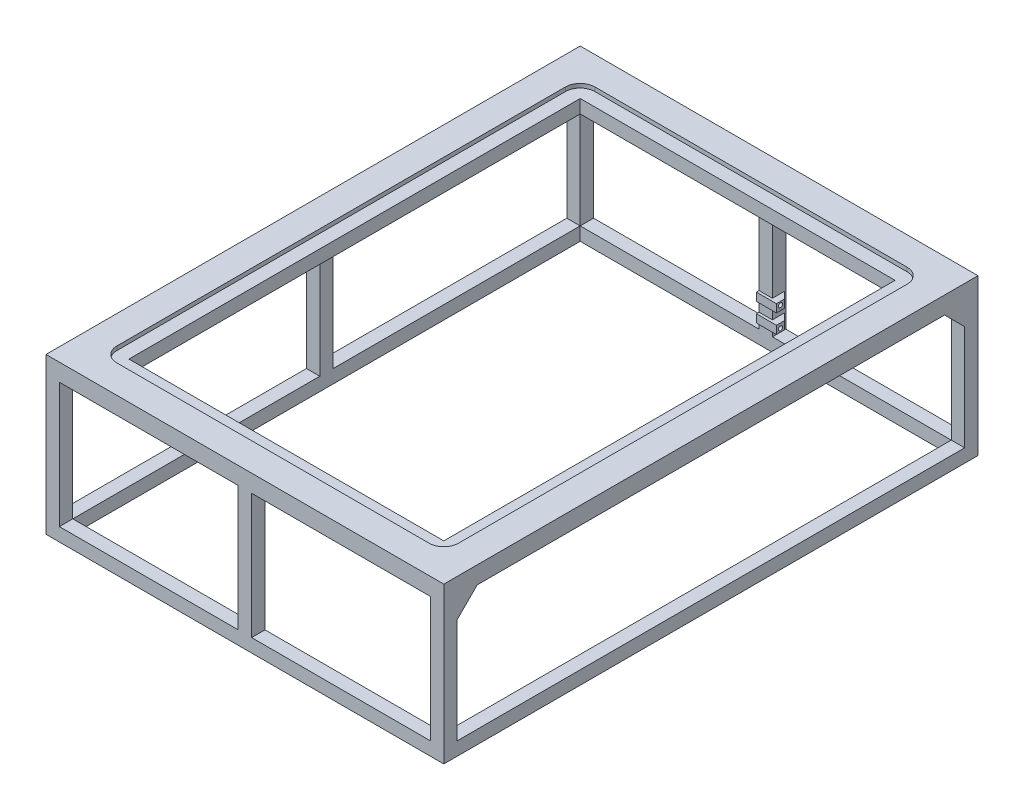
SolidWorks part; units mm, degrees
ref_plane "Front Plane" through (0, 0, 0) normal (0, 0, 1) x (1, 0, 0)
ref_plane "Top Plane" through (0, 0, 0) normal (0, 1, 0) x (1, 0, 0)
ref_plane "Right Plane" through (0, 0, 0) normal (1, 0, 0) x (0, 0, -1)
sketch "Sketch1" plane through (0, 0, 0) normal (0, 1, 0) x (1, 0, 0)
  line L1 (0, 0) -> (253.5, 0)
  line L2 (0, 0) -> (0, 355.5)
  line L3 (0, 355.5) -> (253.5, 355.5)
  line L4 (253.5, 0) -> (253.5, 355.5)
  line L5 (-22, 377.5) -> (275.5, 377.5)
  line L6 (-22, 377.5) -> (-22, -22)
  line L7 (-22, -22) -> (275.5, -22)
  line L8 (275.5, 377.5) -> (275.5, -22)
  line L9 (-12, 367.5) -> (265.5, 367.5)
  line L10 (-12, 367.5) -> (-12, -12)
  line L11 (-12, -12) -> (265.5, -12)
  line L12 (265.5, 367.5) -> (265.5, -12)
  dimension "D1" = 253.5
  dimension "D2" = 355.5
  dimension "D3" = 22
  dimension "D4" = 22
  dimension "D5" = 22
  dimension "D6" = 22
  dimension "D7" = 10
  dimension "D8" = 10
  dimension "D9" = 10
  dimension "D10" = 10
extrude "Boss-Extrude1" add sketch "Sketch1" along normal blind 10 contours L8 L5 L6 L7 L9 L12 L11 L10 region at (126.75, 0, -372.519)
sketch "Sketch2" plane through (0, 10, 0) normal (0, 1, 0) x (1, 0, 0)
  line L0 (-22, -22) -> (275.5, -22) construction
  line L1 (131.75, -22) -> (121.75, -22)
  line L2 (131.75, -22) -> (131.75, -12)
  line L3 (131.75, -12) -> (121.75, -12)
  line L4 (121.75, -22) -> (121.75, -12)
  line L5 (-12, -12) -> (265.5, -12) construction
  line L6 (-12, 367.5) -> (265.5, 367.5) construction
  line L7 (275.5, -22) -> (265.5, -22)
  line L8 (275.5, -22) -> (275.5, -12)
  line L9 (275.5, -12) -> (265.5, -12)
  line L10 (265.5, -22) -> (265.5, -12)
  line L11 (-22, -22) -> (-12, -22)
  line L12 (-22, -22) -> (-22, -12)
  line L13 (-22, -12) -> (-12, -12)
  line L14 (-12, -22) -> (-12, -12)
  line L15 (-22, 377.5) -> (-12, 377.5)
  line L16 (-22, 377.5) -> (-22, 367.5)
  line L17 (-22, 367.5) -> (-12, 367.5)
  line L18 (-12, 377.5) -> (-12, 367.5)
  line L19 (275.5, 377.5) -> (265.5, 377.5)
  line L20 (275.5, 377.5) -> (275.5, 367.5)
  line L21 (275.5, 367.5) -> (265.5, 367.5)
  line L22 (265.5, 377.5) -> (265.5, 367.5)
  line L23 (131.75, 367.5) -> (121.75, 367.5)
  line L24 (131.75, 367.5) -> (131.75, 377.5)
  line L25 (131.75, 377.5) -> (121.75, 377.5)
  line L26 (121.75, 367.5) -> (121.75, 377.5)
  line L27 (-22, 377.5) -> (275.5, 377.5) construction
  line L28 (275.5, 377.5) -> (275.5, -22) construction
  line L29 (275.5, 172.75) -> (265.5, 172.75)
  line L30 (275.5, 172.75) -> (275.5, 182.75)
  line L31 (275.5, 182.75) -> (265.5, 182.75)
  line L32 (265.5, 172.75) -> (265.5, 182.75)
  line L33 (265.5, 367.5) -> (265.5, -12) construction
  line L34 (-12, 367.5) -> (-12, -12) construction
  line L35 (-12, 172.75) -> (-22, 172.75)
  line L36 (-12, 172.75) -> (-12, 182.75)
  line L37 (-12, 182.75) -> (-22, 182.75)
  line L38 (-22, 172.75) -> (-22, 182.75)
  line L39 (-22, 377.5) -> (-22, -22) construction
  dimension "D1" = 133.75
  dimension "D2" = 10
  dimension "D3" = 133.75
  dimension "D4" = 10
  dimension "D5" = 133.75
  dimension "D6" = 10
  dimension "D7" = 184.75
  dimension "D8" = 184.75
  dimension "D9" = 10
  dimension "D10" = 184.75
extrude "Boss-Extrude2" add sketch "Sketch2" along normal blind 93.5
sketch "Sketch3" plane through (0, 103.5, 0) normal (0, 1, 0) x (1, 0, 0)
  line L1 (-22, 377.5) -> (275.5, 377.5)
  line L2 (-22, 377.5) -> (-22, -22)
  line L3 (-22, -22) -> (275.5, -22)
  line L4 (275.5, 377.5) -> (275.5, -22)
  line L9 (244.5, 346.5) -> (9, 346.5)
  line L10 (244.5, 346.5) -> (244.5, 9)
  line L11 (244.5, 9) -> (9, 9)
  line L12 (9, 346.5) -> (9, 9)
  dimension "D1" = 235.5
  dimension "D2" = 337.5
  dimension "D3" = 31
  dimension "D4" = 31
  dimension "D5" = 31
  dimension "D6" = 31
extrude "Boss-Extrude3" add sketch "Sketch3" along normal blind 10
sketch "Sketch4" plane through (0, 0, 0) normal (0, -1, 0) x (1, 0, 0)
  line L0 (-22, -177.75) -> (275.5, -177.75)
  line L1 (-22, -377.5) -> (-22, 22) construction
  line L2 (275.5, -377.5) -> (275.5, 22) construction
  line L3 (126.75, -377.5) -> (126.75, 22)
  line L4 (-22, -377.5) -> (275.5, -377.5) construction
  line L5 (-22, 22) -> (275.5, 22) construction
  line L6 (-17, -377.5) -> (-17, 22)
  line L7 (-22, -377.5) -> (275.5, -377.5)
  line L8 (-22, -377.5) -> (-22, -367.5)
  line L9 (-22, -367.5) -> (275.5, -367.5)
  line L10 (275.5, -377.5) -> (275.5, -367.5)
  line L11 (-22, 22) -> (275.5, 22)
  line L12 (-22, 22) -> (-22, 12)
  line L13 (-22, 12) -> (275.5, 12)
  line L14 (275.5, 22) -> (275.5, 12)
  line L15 (275.5, -377.5) -> (265.5, -377.5)
  line L16 (275.5, -377.5) -> (275.5, 22)
  line L17 (275.5, 22) -> (265.5, 22)
  line L18 (265.5, -377.5) -> (265.5, 22)
  line L19 (-22, -377.5) -> (-12, -377.5)
  line L20 (-22, -377.5) -> (-22, 22)
  line L21 (-22, 22) -> (-12, 22)
  line L22 (-12, -377.5) -> (-12, 22)
  line L23 (-22, 17) -> (275.5, 17)
  line L24 (-22, -372.5) -> (275.5, -372.5)
  line L25 (265.5, -367.5) -> (275.5, -377.5)
  line L26 (265.5, 12) -> (275.5, 22)
  line L27 (-22, -377.5) -> (-12, -367.5)
  line L28 (-12, 12) -> (-22, 22)
  circle A0 centre (270.5, 17) radius 1.6
  circle A1 centre (270.5, -177.75) radius 1.6
  circle A2 centre (270.5, -372.5) radius 1.6
  circle A3 centre (126.75, -372.5) radius 1.6
  circle A4 centre (-17, -372.5) radius 1.6
  circle A5 centre (-17, -177.75) radius 1.6
  circle A6 centre (-17, 17) radius 1.6
  circle A7 centre (126.75, 17) radius 1.6
  dimension "D1" = 3.2
  dimension "D2" = 3.2
  dimension "D3" = 3.2
  dimension "D4" = 3.2
  dimension "D5" = 3.2
  dimension "D6" = 3.2
  dimension "D7" = 3.2
  dimension "D8" = 3.2
extrude "Cut-Extrude1" cut sketch "Sketch4" against normal blind 1.2 contours L26 A0 L23 | L26 A0 L23 | L23 A0 L26 | L23 A0 L26 | L0 A1 | L0 A1 | L24 A2 L25 | L25 A2 L24 | L25 A2 L24 | L24 A2 L25 | L23 A7 L3 | L3 A7 L23 | L3 A7 L23 | L23 A7 L3 | L24 A3 L3 | L3 A3 L24 | L24 A3 L3 | L3 A3 L24 | L23 A6 L6 | L6 A6 L28 | L28 A6 L23 | L23 A6 L6 | L28 A6 L23 | L6 A6 L28 | L0 A5 L6 | L6 A5 L0 | L0 A5 L6 | L6 A5 L0 | L24 A4 L27 | L27 A4 L6 | L6 A4 L24 | L24 A4 L27 | L27 A4 L6 | L6 A4 L24 region at (270.5, 0, -178.4291) region at (270.5, 0, -177.0709) region at (270.8201, 0, -371.7272) region at (269.5397, 0, -372.1022) region at (271.4603, 0, -372.8978) region at (269.5397, 0, 16.6022) region at (270.8201, 0, 16.2272) region at (271.4603, 0, 17.3978) region at (127.4291, 0, -371.8209) region at (126.0709, 0, -371.8209) region at (127.4291, 0, -373.1791) region at (270.1799, 0, -373.2728) region at (126.0709, 0, 16.3209) region at (127.4291, 0, 16.3209) region at (127.4291, 0, 17.6791) region at (270.1799, 0, 17.7728) region at (-16.3209, 0, -178.4291) region at (-16.3209, 0, -177.0709) region at (126.0709, 0, -373.1791) region at (-16.0397, 0, -372.1022) region at (-16.6022, 0, -371.5397) region at (126.0709, 0, 17.6791) region at (-16.6022, 0, 16.0397) region at (-16.0397, 0, 16.6022) region at (-17.6791, 0, -178.4291) region at (-17.6791, 0, -177.0709) region at (-17.6791, 0, -371.8209) region at (-16.3209, 0, -373.1791) region at (-17.9603, 0, -372.8978) region at (-17.3978, 0, -373.4603) region at (-17.6791, 0, 16.3209) region at (-16.3209, 0, 17.6791) region at (-17.3978, 0, 17.9603) region at (-17.9603, 0, 17.3978)
sketch "Sketch6" plane through (0, 113.5, 0) normal (0, 1, 0) x (1, 0, 0)
  line L0 (253.5, 10) -> (253.5, 345.5) construction
  line L1 (10, 0) -> (243.5, 0) construction
  line L2 (0, 345.5) -> (0, 10) construction
  line L3 (243.5, 355.5) -> (10, 355.5) construction
  line L4 (253.5, 10) -> (253.5, 345.5)
  line L5 (10, 0) -> (243.5, 0)
  line L6 (0, 345.5) -> (0, 10)
  line L7 (243.5, 355.5) -> (10, 355.5)
  line L8 (254.5, 10) -> (254.5, 345.5)
  line L9 (243.5, 356.5) -> (10, 356.5)
  line L10 (-1, 345.5) -> (-1, 10)
  line L11 (10, -1) -> (243.5, -1)
  line L13 (275.5, 377.5) -> (-22, 377.5)
  line L14 (275.5, 377.5) -> (275.5, -22)
  line L15 (275.5, -22) -> (-22, -22)
  line L16 (-22, 377.5) -> (-22, -22)
  circle A0 centre (247.5, 349.5) radius 1.6 construction
  circle A1 centre (247.5, 263.625) radius 1.6 construction
  circle A2 centre (247.5, 177.75) radius 1.6 construction
  circle A3 centre (247.5, 91.875) radius 1.6 construction
  circle A4 centre (247.5, 6) radius 1.6 construction
  circle A5 centre (167, 6) radius 1.6 construction
  circle A6 centre (86.5, 6) radius 1.6 construction
  circle A7 centre (6, 6) radius 1.6 construction
  circle A8 centre (6, 91.875) radius 1.6 construction
  circle A9 centre (6, 177.75) radius 1.6 construction
  circle A10 centre (6, 263.625) radius 1.6 construction
  circle A11 centre (6, 349.5) radius 1.6 construction
  circle A12 centre (167, 349.5) radius 1.6 construction
  circle A13 centre (86.5, 349.5) radius 1.6 construction
  circle A14 centre (247.5, 349.5) radius 1.6
  circle A15 centre (247.5, 263.625) radius 1.6
  circle A16 centre (247.5, 177.75) radius 1.6
  circle A17 centre (247.5, 91.875) radius 1.6
  circle A18 centre (247.5, 6) radius 1.6
  circle A19 centre (167, 6) radius 1.6
  circle A20 centre (86.5, 6) radius 1.6
  circle A21 centre (6, 6) radius 1.6
  circle A22 centre (6, 91.875) radius 1.6
  circle A23 centre (6, 177.75) radius 1.6
  circle A24 centre (6, 263.625) radius 1.6
  circle A25 centre (6, 349.5) radius 1.6
  circle A26 centre (167, 349.5) radius 1.6
  circle A27 centre (86.5, 349.5) radius 1.6
  arc A28 (253.5, 345.5) -> (243.5, 355.5) centre (243.5, 345.5) ccw construction
  arc A29 (243.5, 0) -> (253.5, 10) centre (243.5, 10) ccw construction
  arc A30 (0, 10) -> (10, 0) centre (10, 10) ccw construction
  arc A31 (10, 355.5) -> (0, 345.5) centre (10, 345.5) ccw construction
  arc A32 (253.5, 345.5) -> (243.5, 355.5) centre (243.5, 345.5) ccw
  arc A33 (243.5, 0) -> (253.5, 10) centre (243.5, 10) ccw
  arc A34 (0, 10) -> (10, 0) centre (10, 10) ccw
  arc A35 (10, 355.5) -> (0, 345.5) centre (10, 345.5) ccw
  arc A36 (254.5, 345.5) -> (243.5, 356.5) centre (243.5, 345.5) ccw
  arc A37 (10, 356.5) -> (-1, 345.5) centre (10, 345.5) ccw
  arc A38 (-1, 10) -> (10, -1) centre (10, 10) ccw
  arc A39 (243.5, -1) -> (254.5, 10) centre (243.5, 10) ccw
  line M9 (-22, 377.5) -> (-22, -22)
  line M10 (-22, -22) -> (275.5, -22)
  line M11 (275.5, -22) -> (275.5, 377.5)
  line M12 (275.5, 377.5) -> (-22, 377.5)
  dimension "D1" = 1
extrude "Boss-Extrude4" add sketch "Sketch6" along normal up to surface (3 mm away) contours A39 L11 A38 L10 A37 L9 A36 L8 M12 M9 M10 M11 region at (270.519, 113.5, -177.75)
sketch "Sketch7" plane through (275.5, 0, 0) normal (1, 0, 0) x (0, 0, -1)
  line L0 (-12, 103.5) -> (172.75, 103.5) construction
  line L1 (170.75, 103.5) -> (184.75, 103.5)
  line L2 (170.75, 103.5) -> (170.75, 10)
  line L3 (170.75, 10) -> (184.75, 10)
  line L4 (184.75, 103.5) -> (184.75, 10)
  line L5 (367.5, 10) -> (182.75, 10) construction
  line L6 (172.75, 103.5) -> (172.75, 10) construction
  line L7 (182.75, 103.5) -> (182.75, 10) construction
  dimension "D1" = 2
  dimension "D2" = 2
extrude "Cut-Extrude2" cut sketch "Sketch7" against normal blind 16.15
chamfer "Chamfer1" distance 15 angle 45 2 edges at (270.5, 103.5, -367.5) (270.5, 103.5, 12)
sketch "Sketch8" plane through (131.75, 0, 0) normal (1, 0, 0) x (0, 0, -1)
  line L1 (371.5, 35) -> (365.5, 35)
  line L2 (371.5, 35) -> (371.5, 15)
  line L3 (371.5, 15) -> (365.5, 15)
  line L4 (365.5, 35) -> (365.5, 15)
  line L5 (369.5, 35) -> (353.5, 35) construction
  line L6 (371.5, 17) -> (371.5, 33) construction
  line L7 (353.5, 15) -> (369.5, 15) construction
  line L8 (367.5, 103.5) -> (367.5, 10) construction
  line L9 (371.5, 15) -> (365.5, 15)
  line L10 (371.5, 35) -> (365.5, 35)
  line L11 (371.5, 35) -> (371.5, 29)
  line L12 (371.5, 29) -> (365.5, 29)
  line L13 (365.5, 35) -> (365.5, 29)
  line L14 (371.5, 15) -> (371.5, 21)
  line L15 (371.5, 21) -> (365.5, 21)
  line L16 (365.5, 15) -> (365.5, 21)
  line M10 (367.5, 103.5) -> (367.5, 10)
  dimension "D1" = 0
  dimension "D2" = 0
  dimension "D3" = 0
  dimension "D4" = 2
  dimension "D5" = 6
  dimension "D6" = 6
extrude "Boss-Extrude5" add sketch "Sketch8" along normal blind 5 contours L12 L2 L1 M10 | L12 L1 L4 M10 | L2 L15 L3 M10 | L15 L4 L3 M10 region at (131.75, 32, -369.5) region at (131.75, 32, -366.5) region at (131.75, 18, -369.5) region at (131.75, 18, -366.5)
sketch "Sketch10" plane through (131.75, 0, 0) normal (-1, 0, 0) x (0, 0, 1)
  line L0 (-365.5, 21) -> (-367.5, 21) construction
  line L1 (-367.5, 21) -> (-367.5, 15) construction
  line L2 (-367.5, 15) -> (-365.5, 15) construction
  line L3 (-365.5, 15) -> (-365.5, 21) construction
  line L4 (-365.5, 35) -> (-367.5, 35) construction
  line L5 (-367.5, 35) -> (-367.5, 29) construction
  line L6 (-367.5, 29) -> (-365.5, 29) construction
  line L7 (-365.5, 29) -> (-365.5, 35) construction
  line L8 (-365.5, 21) -> (-367.5, 21)
  line L9 (-367.5, 21) -> (-367.5, 15)
  line L10 (-367.5, 15) -> (-365.5, 15)
  line L11 (-365.5, 15) -> (-365.5, 21)
  line L12 (-365.5, 35) -> (-367.5, 35)
  line L13 (-367.5, 35) -> (-367.5, 29)
  line L14 (-367.5, 29) -> (-365.5, 29)
  line L15 (-365.5, 29) -> (-365.5, 35)
extrude "Boss-Extrude6" add sketch "Sketch10" along normal up to surface (10 mm away) up to face at (121.75, 56.75, -372.5)
sketch "Sketch11" plane through (136.75, 0, 0) normal (1, 0, 0) x (0, 0, -1)
  arc A0 (370.05, 17.5) -> (366.95, 17.5) centre (368.5, 17.5) ccw construction
  arc A1 (366.95, 17.5) -> (370.05, 17.5) centre (368.5, 17.5) ccw construction
  arc A2 (370.05, 32.5) -> (366.95, 32.5) centre (368.5, 32.5) ccw construction
  arc A3 (366.95, 32.5) -> (370.05, 32.5) centre (368.5, 32.5) ccw construction
  arc A4 (370.05, 17.5) -> (366.95, 17.5) centre (368.5, 17.5) ccw
  arc A5 (366.95, 17.5) -> (370.05, 17.5) centre (368.5, 17.5) ccw
  arc A6 (370.05, 32.5) -> (366.95, 32.5) centre (368.5, 32.5) ccw
  arc A7 (366.95, 32.5) -> (370.05, 32.5) centre (368.5, 32.5) ccw
extrude "Cut-Extrude4" cut sketch "Sketch11" against normal blind 18
chamfer "Chamfer2" distance 5 angle 45 2 edges at (131.75, 18, -371.5) (131.75, 32, -371.5)
